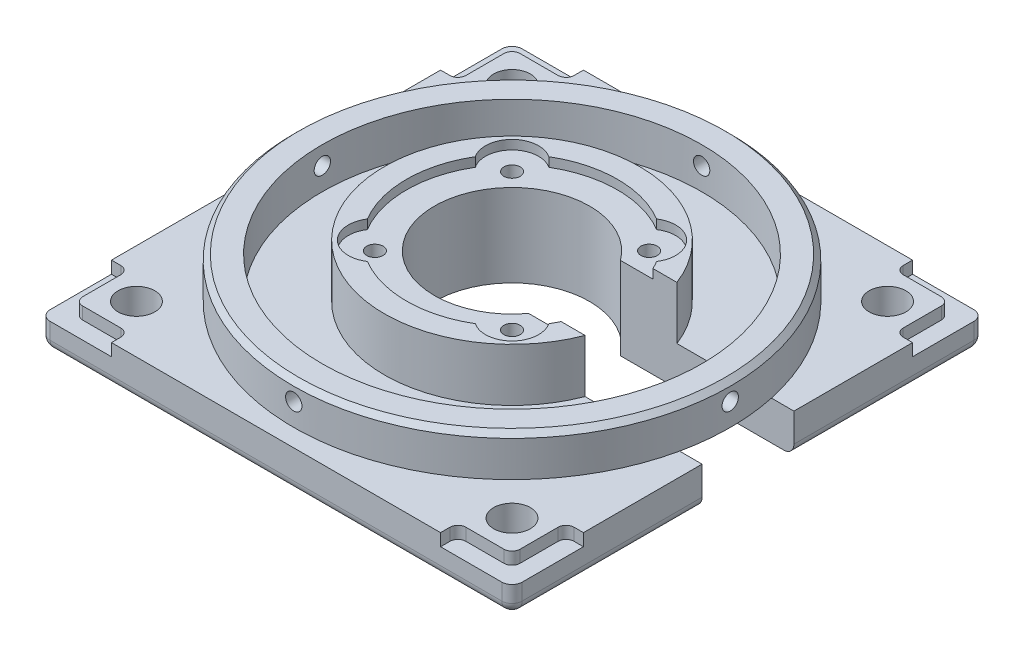
SolidWorks part; units mm, degrees
ref_plane "Front Plane" through (0, 0, 0) normal (0, 0, 1) x (1, 0, 0)
ref_plane "Top Plane" through (0, 0, 0) normal (0, 1, 0) x (1, 0, 0)
ref_plane "Right Plane" through (0, 0, 0) normal (1, 0, 0) x (0, 0, -1)
sketch "Sketch3" plane through (0, 0, 0) normal (0, 1, 0) x (1, 0, 0)
  circle A0 centre (0, 0) radius 7.6
  circle A1 centre (0, 0) radius 12.5
  dimension "D1" = 15.2
  dimension "D2" = 25
extrude "Boss-Extrude2" add sketch "Sketch3" along normal blind 9
sketch "Sketch4" plane through (0, 9, 0) normal (0, 1, 0) x (1, 0, 0)
  line L0 (6.1245, 4.5) -> (6.1245, -4.5)
  line L1 (6.1245, -4.5) -> (13.2817, -4.5)
  line L2 (13.2817, -4.5) -> (13.2817, 4.5)
  line L3 (13.2817, 4.5) -> (6.1245, 4.5)
  circle A0 centre (0, 0) radius 7.6 construction
  point P0 (0, 0)
  point P1 (6.1245, 4.5)
  point P3 (6.1245, -4.5)
  dimension "D1" = 4.5
extrude "Cut-Extrude2" cut sketch "Sketch4" against normal blind 9
sketch "Sketch5" plane through (0, 9, 0) normal (0, 1, 0) x (1, 0, 0)
  line L0 (0, 0) -> (17.4279, 0) construction
  line L1 (0, 0) -> (-11.2462, -11.2462) construction
  line L2 (0, 0) -> (-11.0539, 11.0539) construction
  point P0 (0, 0)
  point P1 (-6.715, 6.72)
  point P3 (-6.715, -6.72)
  point P9 (6.72, -6.715)
  point P10 (6.72, 6.715)
  dimension "D1" = 6.72
  dimension "D2" = 9.5
  dimension "D3" = 6.72
  dimension "D4" = 9.5
sketch "Sketch6" plane through (0, 9, 0) normal (0, 1, 0) x (1, 0, 0)
  line L0 (0, 0) -> (-11.2462, -11.2462) construction
  line L1 (0, 0) -> (-11.0539, 11.0539) construction
  line L2 (0, 0) -> (17.4279, 0) construction
  point P0 (5.2883, -8.8853)
  point P9 (-8.8853, 5.2883)
  point P12 (5.2883, 8.8853)
  point P14 (8.8893, -5.2817)
  point P15 (-5.2817, 8.8893)
  point P16 (8.8893, 5.2817)
  point P17 (-5.2817, -8.8893)
  point P18 (-8.8853, -5.2883)
  dimension "D1" = 2.6
  dimension "D2" = 10.34
  dimension "D3" = 2.6
  dimension "D4" = 10.34
sketch "Sketch8" plane through (0, 9, 0) normal (0, 1, 0) x (1, 0, 0)
  circle A0 centre (0, 0) radius 10.34
extrude "Cut-Extrude5" cut sketch "Sketch8" against normal blind 0.9
hole_wizard "Tap Drill for M2x0.4 Tap1" positions "3DSketch1" profile "Sketch10" hole size "M2x0.4" standard "ANSI Metric" end condition through all
sketch3d "3DSketch1"
  point P0 (6.72, 9, 6.715)
  point P3 (-6.715, 9, 6.72)
  point P6 (-6.715, 9, -6.72)
  point P9 (6.72, 9, -6.715)
sketch "Sketch10" plane through (6.72, 9, 6.715) normal (1, 0, 0) x (0, 0, 1)
  line L0 (0, 0) -> (0, 9)
  line L1 (0, 9) -> (0.8, 9)
  line L2 (0.8, 9) -> (0.8, 0)
  line L5 (0.8, 0) -> (0, 0)
  line L11 (0, -6.35) -> (0, 107.95) construction
  dimension "Thru Hole Dia." = 1.6
  dimension "Thru Hole Depth" = 9
sketch "Sketch11" plane through (0, 9, 0) normal (0, 1, 0) x (1, 0, 0)
  line L0 (8.8893, 5.2817) -> (5.2883, 8.8853)
  line L1 (8.8893, -5.2817) -> (5.2883, -8.8853)
  line L2 (-5.2817, -8.8893) -> (-8.8853, -5.2883)
  line L3 (-5.2817, 8.8893) -> (-8.8853, 5.2883)
  arc A0 (5.2883, -8.8853) -> (8.8893, -5.2817) centre (6.72, -6.715) ccw
  arc A1 (9.3094, 4.5) -> (9.3094, -4.5) centre (0, 0) ccw construction
  arc A2 (8.8893, 5.2817) -> (5.2883, 8.8853) centre (6.72, 6.715) ccw
  arc A3 (-5.2817, 8.8893) -> (-8.8853, 5.2883) centre (-6.715, 6.72) ccw
  arc A4 (-8.8853, -5.2883) -> (-5.2817, -8.8893) centre (-6.715, -6.72) ccw
extrude "Cut-Extrude6" cut sketch "Sketch11" against normal blind 0.9
sketch "Sketch12" plane through (0, 0, 0) normal (0, -1, 0) x (1, 0, 0)
  line L0 (0, 0) -> (17.7684, 0) construction
  line L1 (0, 0) -> (0, 18.0241) construction
  line L2 (23.125, -23.125) -> (-23.125, -23.125)
  line L3 (-23.125, -23.125) -> (-23.125, 23.125)
  line L4 (-23.125, 23.125) -> (23.125, 23.125)
  line L9 (6.4622, 4) -> (23.125, 4)
  line L11 (23.125, -4.5) -> (6.1245, -4.5)
  line L13 (23.125, -23.125) -> (23.125, -4.5)
  line L14 (23.125, 23.125) -> (23.125, 4)
  arc A0 (6.1245, -4.5) -> (6.4622, 4) centre (0, 0) cw
  circle A1 centre (0, 0) radius 7.6 construction
  point P0 (23.125, -23.125)
  point P4 (23.125, 23.125)
  point P5 (-23.125, 23.125)
  point P7 (-23.125, -23.125)
  dimension "D1" = 23.125
  dimension "D2" = 23.125
extrude "Boss-Extrude4" add sketch "Sketch12" against normal blind 3.81
fillet "Fillet2" radius 1 2 edges at (-23.125, 0, 0) (0, 0, 23.125)
fillet "Fillet3" radius 1 2 edges at (-22.8321, 0.2929, 22.8321) (-23.125, 2.405, 23.125)
sketch "Sketch13" plane through (0, 0, 0) normal (0, -1, 0) x (1, 0, 0)
  line L0 (0, 0) -> (-25.0462, 0) construction
  line L1 (0, 0) -> (0, 26.5218) construction
  point P0 (18.3989, -18.3989)
  point P5 (18.3989, 18.3989)
  point P6 (-18.3989, -18.3989)
  point P7 (-18.3989, 18.3989)
  dimension "D1" = 18.3989
  dimension "D2" = 18.3989
hole_wizard "M3 Clearance Hole1" positions "3DSketch2" profile "Sketch14" hole size "M3" standard "ANSI Metric" end condition through all
sketch3d "3DSketch2"
  point P0 (18.3989, 0, 18.3989)
  point P3 (18.3989, 0, -18.3989)
  point P6 (-18.3989, 0, -18.3989)
  point P9 (-18.3989, 0, 18.3989)
sketch "Sketch14" plane through (18.3989, 0, 18.3989) normal (1, 0, 0) x (0, 0, -1)
  line L0 (0, 0) -> (0, 9)
  line L1 (0, 9) -> (1.8, 9)
  line L2 (1.8, 9) -> (1.8, 0)
  line L5 (1.8, 0) -> (0, 0)
  line L11 (0, -6.35) -> (0, 107.95) construction
  dimension "Thru Hole Dia." = 3.6
  dimension "Thru Hole Depth" = 9
fillet "Fillet4" radius 1 7 edges at (23.125, 2.405, 23.125) (23.125, 0.2929, 22.8321) (-23.125, 2.405, -23.125) (-22.8321, 0.2929, -23.125) (23.125, 0, 13.0625) (23.125, 0, -13.8125) (0.5, 0, -23.125)
fillet "Fillet5" radius 1 2 edges at (22.8321, 0.2929, -22.8321) (23.125, 2.405, -23.125)
sketch "Sketch15" plane through (0, 3.81, 0) normal (0, 1, 0) x (1, 0, 0)
  circle A0 centre (0, 0) radius 21.4
  circle A1 centre (0, 0) radius 18.6
  point P0 (0, 0)
  dimension "D1" = 42.8
  dimension "D2" = 2.8
extrude "Boss-Extrude6" add sketch "Sketch15" along normal blind 4
hole_wizard "Tap Drill for M2x0.4 Tap2" positions "3DSketch4" profile "Sketch25" hole size "M2x0.4" standard "ANSI Metric" end condition up to next
sketch3d "3DSketch4"
  point P0 (21.4, 6.01, 0)
  dimension "D1" = 2.2
sketch "Sketch25" plane through (21.4, 6.01, 0) normal (0, 1, 0) x (0, 0, -1)
  line L0 (0, 0) -> (0, 2.8)
  line L1 (0, 2.8) -> (0.8, 2.8)
  line L2 (0.8, 2.8) -> (0.8, 0)
  line L5 (0.8, 0) -> (0, 0)
  line L11 (0, -6.35) -> (0, 107.95) construction
  dimension "Thru Hole Dia." = 1.6
  dimension "Thru Hole Depth" = 2.8
ref_axis "Axis1" through (0, 8.1, 0) along (0, -1, 0)
pattern_circular "CirPattern1" count 4 over 360 about axis through (0, 8.1, 0) along (0, -1, 0) of "Tap Drill for M2x0.4 Tap2"
chamfer "Chamfer1" distance 0.5 angle 45 1 edges at (0, 7.81, 21.4)
sketch "Sketch26" plane through (0, 3.81, 0) normal (0, 1, 0) x (1, 0, 0)
  line L1 (6.1245, -4.5) -> (23.125, -4.5)
  line L2 (6.1245, -4.5) -> (6.1245, 4.5)
  line L3 (6.1245, 4.5) -> (23.125, 4.5)
  line L4 (23.125, -4.5) -> (23.125, 4.5)
extrude "Cut-Extrude7" cut sketch "Sketch26" against normal up to next
sketch "Sketch27" plane through (0, 3.81, 0) normal (0, 1, 0) x (1, 0, 0)
  line L5 (22.125, -23.125) -> (-22.125, -23.125) construction
  line L6 (16.125, -23.125) -> (23.125, -23.125)
  line L11 (16.125, -23.125) -> (16.125, -21.425)
  line L12 (16.125, -21.425) -> (21.425, -21.425)
  line L13 (23.125, -23.125) -> (23.125, -21.425)
  line L14 (23.125, -4.5) -> (23.125, -22.125) construction
  line L16 (23.125, -23.125) -> (21.425, -23.125)
  line L17 (23.125, -23.125) -> (23.125, -16.125)
  line L18 (23.125, -16.125) -> (21.425, -16.125)
  line L19 (21.425, -21.425) -> (21.425, -16.125)
  line M18 (-22.125, -23.125) -> (22.125, -23.125)
  arc M19 (22.125, -23.125) -> (23.125, -22.125) centre (22.125, -22.125) ccw
  line M20 (23.125, -22.125) -> (23.125, -4.5)
extrude "Cut-Extrude9" cut sketch "Sketch27" against normal blind 1.2 contours L19 L12 L11 L6 L18 M18 M19 M20 region at (16.224, 3.81, 22.275)
fillet "Fillet6" radius 0.787 3 edges at (21.425, 3.21, 16.125) (21.425, 3.21, 21.425) (16.125, 3.21, 21.425)
pattern_circular "CirPattern4" count 4 over 360 about axis through (0, 8.1, 0) along (0, -1, 0) of "Cut-Extrude9", "Fillet6"
